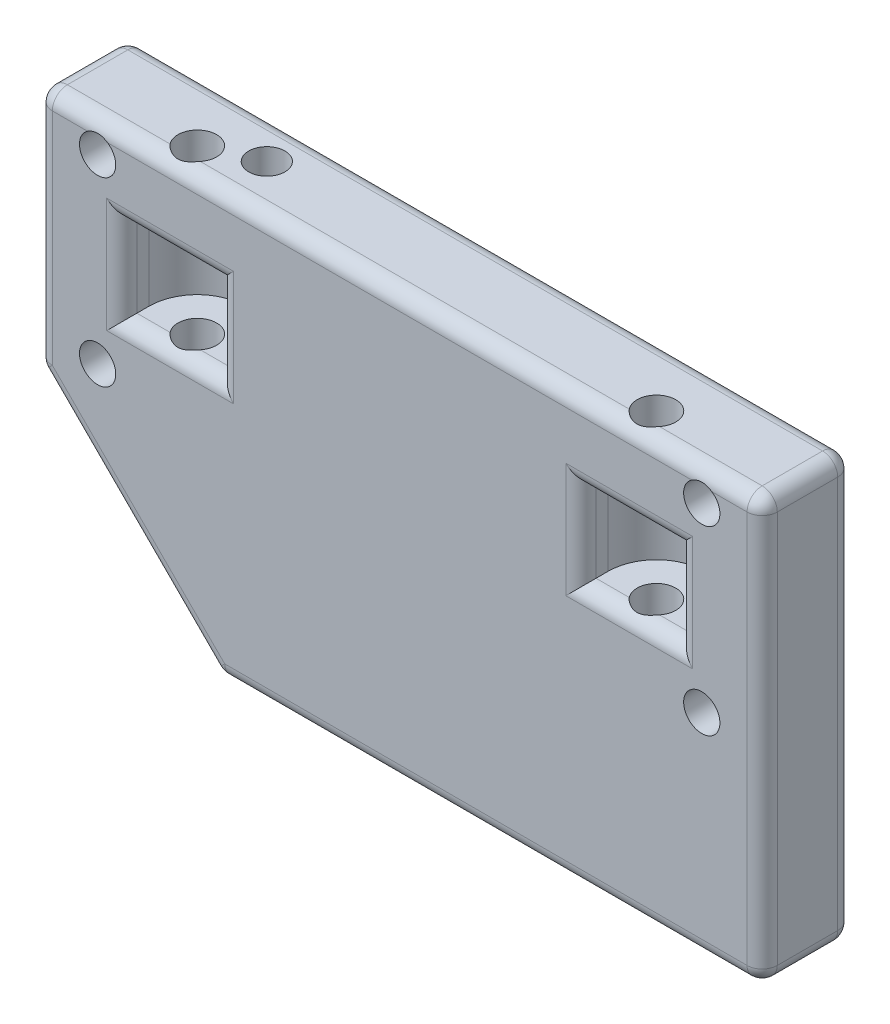
SolidWorks part; units mm, degrees
ref_plane "Front Plane" through (0, 0, 0) normal (0, 0, 1) x (1, 0, 0)
ref_plane "Top Plane" through (0, 0, 0) normal (0, 1, 0) x (1, 0, 0)
ref_plane "Right Plane" through (0, 0, 0) normal (1, 0, 0) x (0, 0, -1)
sketch "Sketch1" plane through (0, 0, 0) normal (0, 0, 1) x (1, 0, 0)
  line L0 (0, 0) -> (19.05, -19.05)
  line L2 (0, 0) -> (0, 25.4)
  line L3 (0, 25.4) -> (76.2, 25.4)
  line L5 (19.05, -19.05) -> (76.2, -19.05)
  line L10 (76.2, -19.05) -> (76.2, 25.4)
  dimension "D1" = 76.2
  dimension "D2" = 25.4
  dimension "D3" = 19.05
  dimension "D4" = 19.05
extrude "Boss-Extrude1" add sketch "Sketch1" along normal blind 9.525
ref_plane "Plane1" through (0, 12.7, 0) normal (0, 1, 0) x (1, 0, 0)
ref_plane "Plane2" through (38.1, 0, 0) normal (1, 0, 0) x (0, 0, -1)
sketch "Sketch2" plane through (0, 0, 9.525) normal (0, 0, 1) x (1, 0, 0)
  line L1 (0, 25.4) -> (0, 0) construction
  circle A0 centre (6.35, 22.225) radius 1.905
  dimension "D1" = 3.81
  dimension "D2" = 22.225
  dimension "D3" = 6.35
extrude "Cut-Extrude1" cut sketch "Sketch2" against normal through all
sketch "Sketch4" plane through (0, 12.7, 0) normal (0, 1, 0) x (1, 0, 0)
  line L7 (76.2, -9.525) -> (0, -9.525) construction
  line L8 (8.89, -6.6675) -> (8.89, -9.525)
  line L9 (19.05, -6.6675) -> (19.05, -9.525)
  line L10 (19.05, -9.525) -> (8.89, -9.525)
  line L11 (0, -9.525) -> (0, 0) construction
  arc A2 (19.05, -6.6675) -> (8.89, -6.6675) centre (13.97, -6.6675) ccw
  dimension "D1" = 10.16
  dimension "D2" = 2.8575
  dimension "D3" = 13.97
extrude "Cut-Extrude2" cut sketch "Sketch4" against normal mid plane 8.89
sketch "Sketch5" plane through (0, 25.4, 0) normal (0, 1, 0) x (1, 0, 0)
  line L0 (76.2, -9.525) -> (0, -9.525) construction
  line L1 (0, -9.525) -> (0, 0) construction
  circle A0 centre (13.97, -6.6675) radius 2.032
  dimension "D3" = 4.064
  dimension "D1" = 2.8575
  dimension "D2" = 13.97
extrude "Cut-Extrude3" cut sketch "Sketch5" against normal blind 28.575
sketch "Sketch13" plane through (0, 0, 0) normal (-1, 0, 0) x (0, 0, 1)
  line L0 (9.525, 25.4) -> (0, 25.4) construction
  line L1 (4.7625, 12.7) -> (0, 12.7) construction
  line L4 (4.7625, 12.7) -> (9.525, 12.7) construction
  circle A0 centre (4.7625, 12.7) radius 1.905
  dimension "D1" = 3.81
  dimension "D2" = 12.7
extrude "Cut-Extrude8" cut sketch "Sketch13" against normal blind 6.35
sketch "Sketch14" plane through (0, 0, 0) normal (0, 0, -1) x (-1, 0, 0)
  line L0 (-76.2, 25.4) -> (0, 25.4) construction
  line L1 (0, 25.4) -> (0, 0) construction
  circle A0 centre (-25.4, 22.225) radius 2.032
  dimension "D2" = 4.064
  dimension "D1" = 3.175
  dimension "D3" = 25.4
extrude "Cut-Extrude9" cut sketch "Sketch14" against normal blind 6.35
sketch "Sketch15" plane through (0, -19.05, 0) normal (0, -1, 0) x (1, 0, 0)
  line L0 (0, 9.525) -> (0, 0) construction
  line L1 (25.4, 0) -> (25.4, 4.7625) construction
  line L2 (19.05, 0) -> (76.2, 0) construction
  line L3 (25.4, 4.7625) -> (25.4, 9.525) construction
  line L4 (19.05, 9.525) -> (76.2, 9.525) construction
  circle A0 centre (25.4, 4.7625) radius 2.032
  dimension "D2" = 4.064
  dimension "D1" = 25.4
extrude "Cut-Extrude10" cut sketch "Sketch15" against normal blind 6.35
sketch "Sketch16" plane through (0, 25.4, 0) normal (0, 1, 0) x (1, 0, 0)
  line L0 (0, -9.525) -> (0, 0) construction
  line L1 (19.05, -4.4406) -> (19.05, 0.6437) construction
  line L2 (19.05, -4.4406) -> (19.05, -9.525) construction
  line L3 (76.2, 0) -> (0, 0) construction
  circle A0 centre (19.05, -4.4406) radius 1.905
  dimension "D2" = 3.81
  dimension "D1" = 19.05
extrude "Cut-Extrude11" cut sketch "Sketch16" against normal blind 6.35
mirror "Mirror1" about plane through (0, 12.7, 0) normal (0, 1, 0) of "Cut-Extrude1"
mirror "Mirror2" about plane through (38.1, 0, 0) normal (1, 0, 0) of "Cut-Extrude10", "Cut-Extrude9", "Cut-Extrude2", "Cut-Extrude1", "Mirror1", "Cut-Extrude3"
fillet "Fillet2" radius 1.5875 23 edges at (0, 0, 4.7625) (9.525, -9.525, 9.525) (19.05, -19.05, 4.7625) (9.525, -9.525, 0) (0, 25.4, 4.7625) (38.1, 25.4, 0) (0, 12.7, 0) (0, 12.7, 9.525) (47.625, -19.05, 9.525) (47.625, -19.05, 0) (62.23, 8.255, 9.525) (67.31, 12.7, 9.525) (62.23, 17.145, 9.525) (57.15, 12.7, 9.525) (19.05, 12.7, 9.525) (13.97, 17.145, 9.525) (8.89, 12.7, 9.525) (13.97, 8.255, 9.525) (38.1, 25.4, 9.525) (76.2, 3.175, 9.525) (76.2, 25.4, 4.7625) (76.2, 3.175, 0) (76.2, -19.05, 4.7625)
